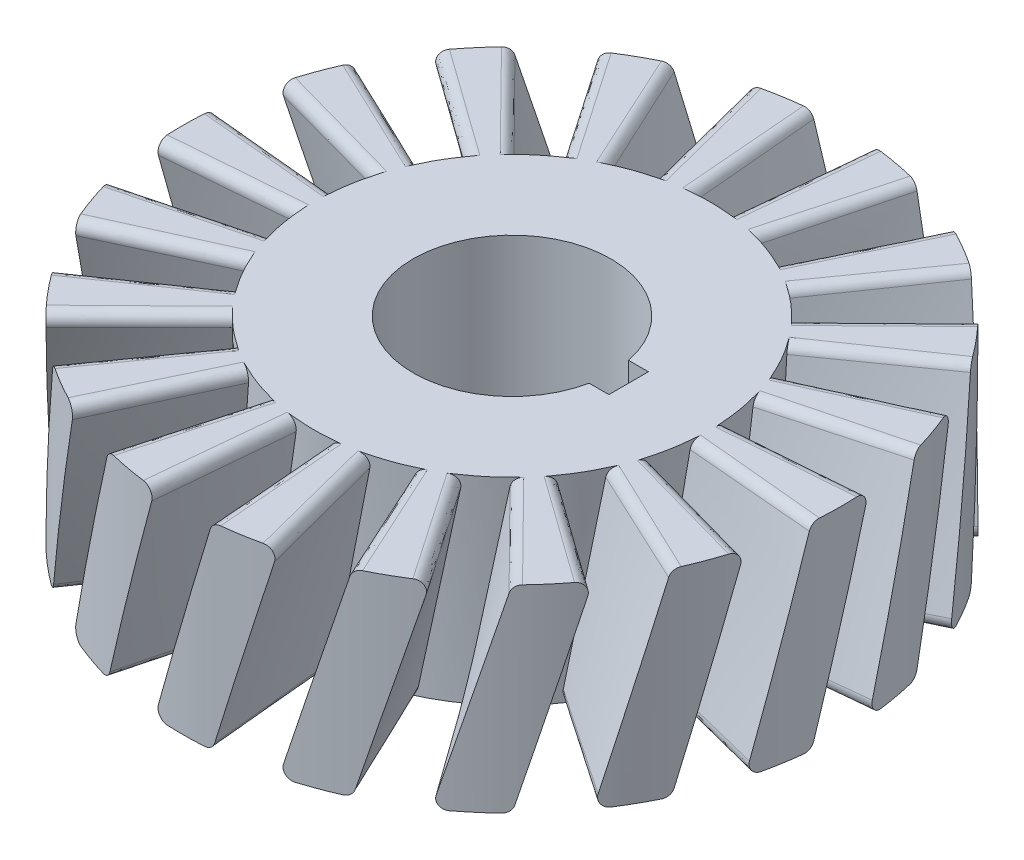
SolidWorks part; units mm, degrees
material "1023 Carbon Steel Sheet (SS)"
ref_plane "Front Plane" through (0, 0, 0) normal (0, 0, 1) x (1, 0, 0)
ref_plane "Top Plane" through (0, 0, 0) normal (0, 1, 0) x (1, 0, 0)
ref_plane "Right Plane" through (0, 0, 0) normal (1, 0, 0) x (0, 0, -1)
sketch "Sketch1" plane through (0, 0, 0) normal (0, 1, 0) x (1, 0, 0)
  circle A0 centre (0, 0) radius 50
  dimension "D1" = 100
extrude "Boss-Extrude1" add sketch "Sketch1" along normal blind 30
sketch "Sketch2" plane through (0, 30, 0) normal (0, 1, 0) x (1, 0, 0)
  circle A0 centre (0, 0) radius 15
  dimension "D1" = 30
extrude "Cut-Extrude1" cut sketch "Sketch2" against normal through all
ref_axis "Axis1" through (0, -0.7, 0) along (0, 1, 0)
sketch "Sketch4" plane through (0, 0, 0) normal (0, 1, 0) x (1, 0, 0)
  line L0 (0, 0) -> (50, 0) construction
  line L1 (0, 0) -> (49.8097, 4.3578) construction
  line L2 (0, 0) -> (49.8097, -4.3578) construction
  line L3 (29.8858, 2.6147) -> (50.8059, 4.4449)
  line L4 (29.8858, -2.6147) -> (50.8059, -4.4449)
  circle A0 centre (0, 0) radius 50 construction
  arc A1 (29.8858, 2.6147) -> (29.8858, -2.6147) centre (0, 0) cw
  arc A2 (50.8059, 4.4449) -> (50.8059, -4.4449) centre (0, 0) cw
  circle A3 centre (0, 0) radius 15 construction
  circle A5 centre (0, 0) radius 50 construction
  dimension "D1" = 10
  dimension "D2" = 15
  dimension "D3" = 1
sketch "Sketch7" plane through (0, 30, 0) normal (0, 1, 0) x (1, 0, 0)
  line L0 (0, 0) -> (49.2404, 8.6824) construction
  line L1 (0, 0) -> (49.8097, 4.3578) construction
  line L2 (0, 0) -> (48.2963, 12.941) construction
  line L3 (0, 0) -> (50, 0) construction
  line L4 (28.9778, 7.7646) -> (49.2622, 13.1998)
  line L5 (29.8858, 2.6147) -> (50.8059, 4.4449)
  circle A0 centre (0, 0) radius 50 construction
  arc A1 (28.9778, 7.7646) -> (29.8858, 2.6147) centre (0, 0) cw
  arc A2 (49.2622, 13.1998) -> (50.8059, 4.4449) centre (0, 0) cw
  arc A3 (50.8059, -4.4449) -> (50.8059, 4.4449) centre (0, 0) ccw construction
  arc A4 (29.8858, -2.6147) -> (29.8858, 2.6147) centre (0, 0) ccw construction
  dimension "D1" = 10
  dimension "D2" = 10
loft "Cut-Loft1" cut profiles "Sketch4", "Sketch7"
fillet "Fillet2" radius 1.5 4 edges at (39.8478, 0, -3.4862)
pattern_circular "CirPattern3" count 18 over 360 about axis through (0, -0.7, 0) along (0, 1, 0) of "Cut-Loft1", "Fillet2"
sketch "Sketch8" plane through (0, 0, 0) normal (0, 1, 0) x (1, 0, 0)
  line L0 (26.3356, 0) -> (18.0347, 0) construction
  line L1 (14.6969, 3) -> (17.6969, 3)
  line L2 (17.6969, 3) -> (17.6969, -3)
  line L3 (17.6969, -3) -> (14.6969, -3)
  arc A0 (14.6969, 3) -> (14.6969, -3) centre (0, 0) cw
  circle A1 centre (0, 0) radius 15 construction
  dimension "D1" = 3
  dimension "D2" = 6
extrude "Cut-Extrude2" cut sketch "Sketch8" along normal through all
equation "\"Vane_opening\"= 10"
equation "\"D1@Sketch4\"=\"Vane_opening\""
equation "\"D1@Sketch7\"=\"Vane_opening\""
equation "\"Vane_spacing\"= 180 / \"Vane_opening\""
